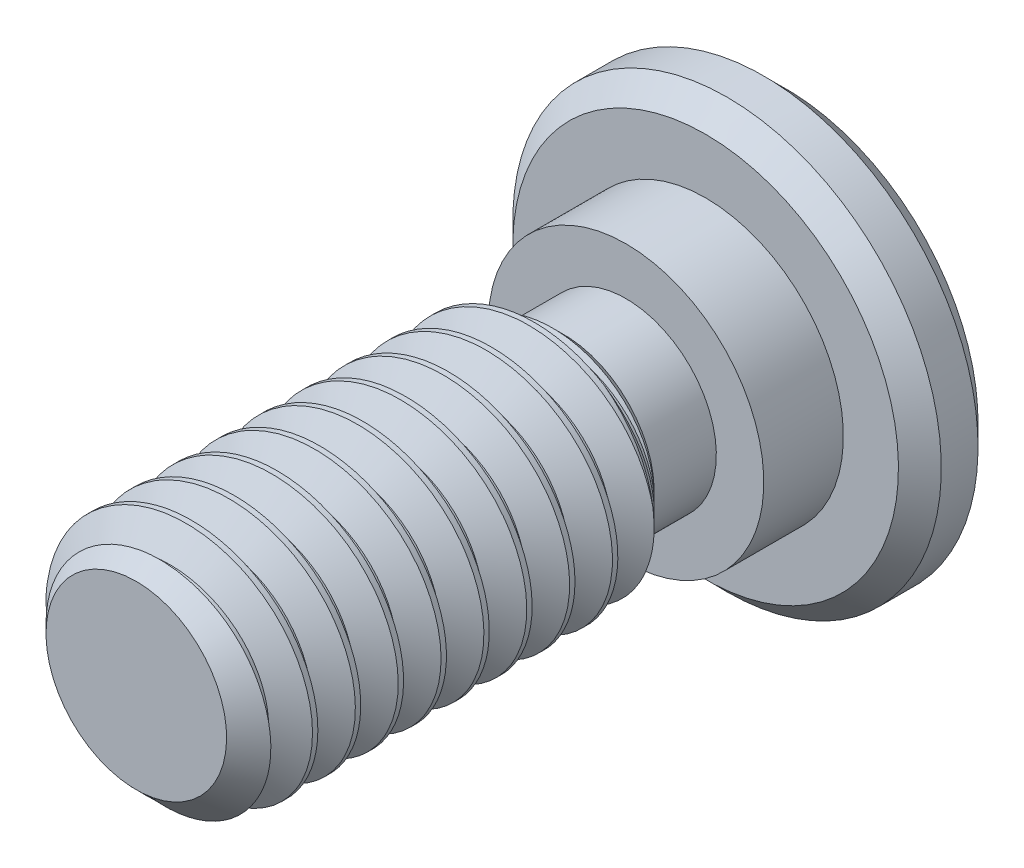
SolidWorks part; units mm, degrees
other "DetailItem1"
ref_plane "Front Plane" through (0, 0, 0) normal (0, 0, 1) x (1, 0, 0)
ref_plane "Top Plane" through (0, 0, 0) normal (0, 1, 0) x (1, 0, 0)
ref_plane "Right Plane" through (0, 0, 0) normal (1, 0, 0) x (0, 0, -1)
sketch "Sketch1" plane through (0, 0, 0) normal (1, 0, 0) x (0, 0, -1)
  line L0 (0, 0) -> (-9.3, 0) construction
  line L1 (0, 0) -> (1.3, 0) construction
  line L2 (1.3, 3.5) -> (1.3, -3.5) construction
  line L3 (-9.3, 2) -> (-9.3, -2) construction
  line L4 (0, 2.25) -> (0, -2.25) construction
  line L5 (-9.3, 2) -> (-8.6, 2) construction
  line L6 (1.3, 1.25) -> (1.3, -1.25) construction
  line L7 (0, 2.25) -> (-1.3, 2.25) construction
  line L8 (-1.3, 2.25) -> (-1.3, 1.475) construction
  line L9 (-1.3, 1.475) -> (-2.316, 1.475) construction
  line L10 (-2.316, 1.475) -> (-2.841, 2) construction
  point P2 (-6.85, -2)
  point P4 (-1.3, 0)
  point P8 (1.3, 0)
  point P11 (-9.3, 0)
  point P14 (0, 0)
  point P19 (1.3, 0)
  dimension "Thread Diameter" = 4
  dimension "Head Diameter" = 7
  dimension "Head Height" = 1.3
  dimension "Shoulder Diameter" = 4.5
  dimension "Shoulder Length" = 1.3
  dimension "Thread Pitch" = 0.7
  dimension "Drive Size" = 2.5
  dimension "D1" = 2.45
  dimension "D2" = 45
  dimension "Undercut Length" = 1.016
  dimension "D3" = 2.95
  dimension "Length" = 8
sketch "Sketch13" plane through (0, 0, 0) normal (1, 0, 0) x (0, 0, -1)
  line L0 (1.3, 3.5) -> (0, 3.5)
  line L1 (0, 3.5) -> (0, 2.25)
  line L3 (-9.3, 2) -> (-9.3, 0)
  line L4 (-9.3, 0) -> (1.3, 0)
  line L5 (1.3, 0) -> (1.3, 3.5)
  line L6 (-2.316, 1.475) -> (-2.841, 2) construction
  line L7 (-1.3, 1.475) -> (-2.316, 1.475) construction
  line L8 (-1.3, 2.25) -> (-1.3, 1.475) construction
  line L9 (0, 2.25) -> (-1.3, 2.25) construction
  line L10 (-2.316, 1.475) -> (-2.841, 2)
  line L11 (-1.3, 1.475) -> (-2.316, 1.475)
  line L12 (-1.3, 2.25) -> (-1.3, 1.475)
  line L13 (0, 2.25) -> (-1.3, 2.25)
  line L14 (-2.841, 2) -> (-9.3, 2)
revolve "Revolve1" add sketch "Sketch13" angle 360 about L4
sketch "Sketch2" plane through (0, 0, 9.3) normal (0, 0, 1) x (1, 0, 0)
  circle A2 centre (0, 0) radius 2
chamfer "Chamfer2" distance 0.525 angle 45 1 edges at (0, -2, 9.3)
sketch "Sketch3" plane through (0, 0, 0) normal (1, 0, 0) x (0, 0, -1)
  line L0 (-9.2563, 2.0758) -> (-9.9563, 2.0758) construction
  line L1 (-9.9563, 2.0758) -> (-9.6063, 1.4696) construction
  line L2 (-9.6063, 1.4696) -> (-9.2563, 2.0758) construction
  line L4 (-9.3, 2) -> (-9.9125, 2) construction
  line L5 (-9.6063, 2.0758) -> (-9.6063, 2) construction
  line L6 (-9.9344, 2.0379) -> (-9.2781, 2.0379)
  line L7 (-9.2781, 2.0379) -> (-9.9344, 2.0379) construction
  line L8 (-9.5625, 1.5453) -> (-9.65, 1.5453) construction
  line L9 (-9.6063, 1.5453) -> (-9.6063, 1.4696) construction
  line L10 (-9.2781, 2.0379) -> (-9.5625, 1.5453)
  line L11 (-9.5625, 1.5453) -> (-9.65, 1.5453)
  line L12 (-9.65, 1.5453) -> (-9.9344, 2.0379)
  point P16 (-9.6063, 2.0379)
  dimension "D1" = 0.7
  dimension "D2" = 0.0875
sketch "Sketch7" plane through (0, 0, -1.3) normal (0, 0, -1) x (-1, 0, 0)
  line L1 (0, 1.4434) -> (-1.25, 0.7217)
  line L2 (-1.25, 0.7217) -> (-1.25, -0.7217)
  line L3 (-1.25, -0.7217) -> (0, -1.4434)
  line L4 (0, -1.4434) -> (1.25, -0.7217)
  line L5 (1.25, -0.7217) -> (1.25, 0.7217)
  line L6 (1.25, 0.7217) -> (0, 1.4434)
  circle A0 centre (0, 0) radius 1.25 construction
extrude "Cut-Extrude1" cut sketch "Sketch7" against normal blind 1.875
chamfer "Chamfer1" distance 0.35 angle 45 2 edges at (0, -3.5, -1.3) (0, -3.5, 0)
sketch "Sketch8" plane through (0, 0, -1.3) normal (0, 0, -1) x (-1, 0, 0)
  circle A0 centre (0, 0) radius 1.4434
extrude "Cut-Extrude2" cut sketch "Sketch8" against normal through all draft 45
curve "Helix/Spiral1" pitch 0.7 height 7.9 radius 2 centre (0, 0, 9.3) axis (0, 0, -1) start towards (0, 1, 0) parameters "pitch"=0.7
sweep "Cut-Sweep1" cut profiles "Sketch3" path "Helix/Spiral1"
equation "\"D3@Helix/Spiral1\"=\"Length@Sketch1\"-.1"
equation "\"D1@Cut-Extrude1\" = \"Drive Size@Sketch1\" * .75"
equation "\"D1@Chamfer1\" = \"Head Diameter@Sketch1\" * .05"
equation "\"D1@Chamfer2\"=\"pitch@Helix/Spiral1\"*.750"
equation "\"D1@Sketch3\" = \"Thread Pitch@Sketch1\""
equation "\"D2@Sketch3\"=\"D1@Sketch3\"/ 1/8"
equation "\"pitch@Helix/Spiral1\" = \"Thread Pitch@Sketch1\""
equation "\"D1@Sketch1\" = \"Thread Pitch@Sketch1\" * 3.5"
equation "\"D3@Sketch1\"=\"Thread Diameter@Sketch1\"-(\"Thread Pitch@Sketch1\"*1.5)"
